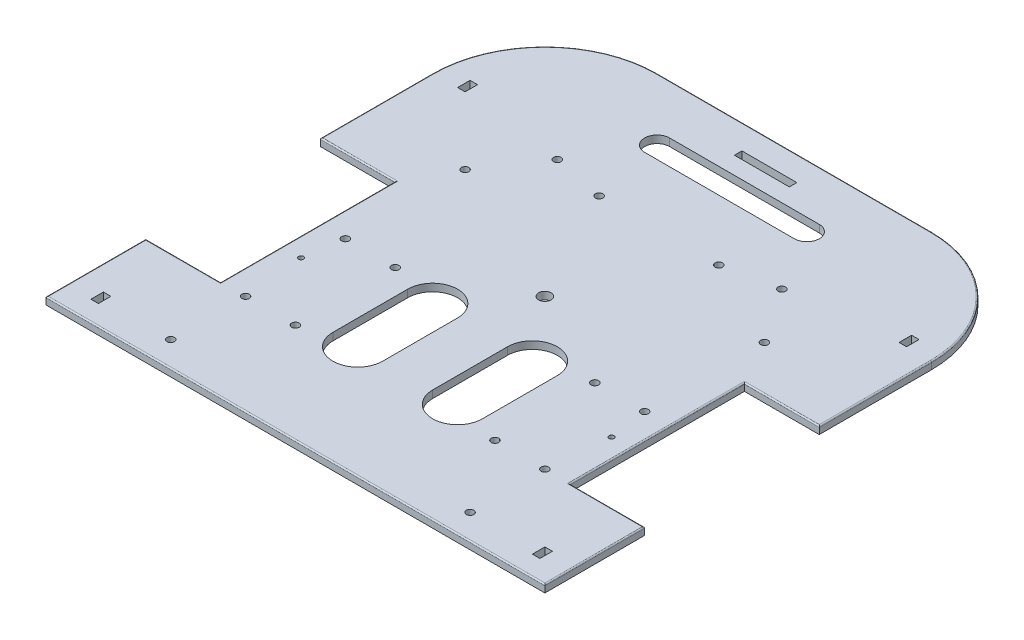
SolidWorks part; units mm, degrees
ref_plane "Front" through (0, 0, 0) normal (0, 0, 1) x (1, 0, 0)
ref_plane "Top" through (0, 0, 0) normal (0, 1, 0) x (1, 0, 0)
ref_plane "Right" through (0, 0, 0) normal (1, 0, 0) x (0, 0, -1)
sketch "Sketch1" plane through (0, 0, 0) normal (0, 1, 0) x (1, 0, 0)
  line L1 (100, -100) -> (-100, -100)
  line L2 (100, -100) -> (100, 100)
  line L3 (100, 100) -> (-100, 100)
  line L4 (-100, -100) -> (-100, 100)
  line L5 (100, -100) -> (-100, 100) construction
  line L6 (100, 100) -> (-100, -100) construction
  point P0 (0, 0)
  dimension "D1" = 200
  dimension "200mm" = 200
extrude "Boss-Extrude1" add sketch "Sketch1" along normal blind 3
ref_plane "Plane1" through (0, 0, 0) normal (1, 0, 0) x (0, 0, -1)
sketch "Sketch2" plane through (0, 3, 0) normal (0, 1, 0) x (1, 0, 0)
  line L0 (-100, 100) -> (-100, -100) construction
  line L1 (-70, 10) -> (-100, 10)
  line L2 (-70, 10) -> (-70, -60)
  line L3 (-70, -60) -> (-100, -60)
  line L4 (-100, 10) -> (-100, -60)
  line L5 (-100, -100) -> (100, -100) construction
  dimension "D1" = 40
  dimension "D2" = 30
  dimension "50" = 70
extrude "Cut-Extrude1" cut sketch "Sketch2" against normal through all and the other way blind 10
sketch "Sketch4" plane through (0, 3, 0) normal (0, 1, 0) x (1, 0, 0)
  line L1 (-87, -92) -> (-90, -92)
  line L2 (-87, -92) -> (-87, -87)
  line L3 (-87, -87) -> (-90, -87)
  line L4 (-90, -92) -> (-90, -87)
  line L5 (-87, -92) -> (-90, -87) construction
  line L6 (-87, -87) -> (-90, -92) construction
  line L7 (-100, -100) -> (100, -100) construction
  line L10 (-100, -60) -> (-100, -100) construction
  dimension "D1" = 5
  dimension "D2" = 3
  dimension "D3" = 10
  dimension "D4" = 8
  dimension "D5" = 5
  dimension "D6" = 5
extrude "Cut-Extrude2" cut sketch "Sketch4" against normal through all
sketch "Sketch5" plane through (0, 3, 0) normal (0, 1, 0) x (1, 0, 0)
  line L0 (-100, 100) -> (-100, 10) construction
  line L1 (-90, 55) -> (-87, 55)
  line L2 (-90, 55) -> (-90, 60)
  line L3 (-90, 60) -> (-87, 60)
  line L4 (-87, 55) -> (-87, 60)
  line L5 (-90, 55) -> (-87, 60) construction
  line L6 (-90, 60) -> (-87, 55) construction
  line L7 (-70, 10) -> (-100, 10) construction
  dimension "D1" = 5
  dimension "D2" = 3
  dimension "D3" = 10
  dimension "D4" = 45
extrude "Cut-Extrude3" cut sketch "Sketch5" against normal through all
sketch "Sketch7" plane through (0, 3, 0) normal (0, 1, 0) x (1, 0, 0)
  line L0 (-20, -55) -> (-20, -25) construction
  line L1 (-30, -55) -> (-30, -25)
  line L2 (-10, -55) -> (-10, -25)
  line L3 (-70, -60) -> (-70, 10) construction
  line L4 (-100, -100) -> (100, -100) construction
  arc A0 (-30, -55) -> (-10, -55) centre (-20, -55) ccw
  arc A1 (-10, -25) -> (-30, -25) centre (-20, -25) ccw
  point P2 (-20, -40)
  dimension "D2" = 10
  dimension "D4" = 30
  dimension "D1" = 30
  dimension "D3" = 50
  dimension "D5" = 60
extrude "Cut-Extrude4" cut sketch "Sketch7" against normal through all
fillet "Fillet1" radius 45 2 edges at (100, 1.5, -100) (-100, 1.5, -100)
sketch "Sketch9" plane through (0, 3, 0) normal (0, 1, 0) x (1, 0, 0)
  line L0 (-100, -60) -> (-100, -100) construction
  line L1 (-100, -100) -> (100, -100) construction
  line L2 (-30, 75) -> (30, 75) construction
  line L3 (-30, 80) -> (30, 80)
  line L4 (-30, 70) -> (30, 70)
  line L5 (-100, 55) -> (-100, 10) construction
  line L6 (55, 100) -> (-55, 100) construction
  line L8 (11, 90) -> (-11, 90)
  line L9 (11, 90) -> (11, 87)
  line L10 (11, 87) -> (-11, 87)
  line L11 (-11, 90) -> (-11, 87)
  line L12 (11, 90) -> (-11, 87) construction
  line L13 (11, 87) -> (-11, 90) construction
  circle A0 centre (-60, -90) radius 1.5
  arc A1 (-30, 80) -> (-30, 70) centre (-30, 75) ccw
  arc A2 (30, 70) -> (30, 80) centre (30, 75) ccw
  point P8 (0, 75)
  point P17 (0, 88.5)
  dimension "D1" = 3
  dimension "D6" = 5
  dimension "D2" = 40
  dimension "D3" = 10
  dimension "D4" = 60
  dimension "D5" = 100
  dimension "D7" = 20
  dimension "D9" = 22
  dimension "D10" = 3
  dimension "D11" = 100
  dimension "D12" = 10
sketch "Sketch10" plane through (0, 3, 0) normal (0, 1, 0) x (1, 0, 0)
  line L0 (-100, -60) -> (-100, -100) construction
  line L1 (-100, -100) -> (100, -100) construction
  circle A0 centre (-60, -60) radius 1.5
  dimension "D1" = 3
  dimension "D2" = 40
  dimension "D3" = 40
sketch "Sketch11" plane through (0, 3, 0) normal (0, 1, 0) x (1, 0, 0)
  line L0 (55, 100) -> (-55, 100) construction
  line L1 (-100, 55) -> (-100, 10) construction
  circle A0 centre (-45, 50) radius 1.5
  dimension "D1" = 3
  dimension "D2" = 50
  dimension "D3" = 55
extrude "Cut-Extrude7" cut sketch "Sketch9" against normal through all
extrude "Cut-Extrude8" cut sketch "Sketch11" against normal through all
extrude "Cut-Extrude9" cut sketch "Sketch10" against normal through all
pattern_linear "LPattern1" count 2 spacing 40 along (0, 0, -1) count 2 spacing 20 along (1, 0, 0) of "Cut-Extrude9"
sketch "Sketch13" plane through (0, 3, 0) normal (0, 1, 0) x (1, 0, 0)
  line L0 (-100, 55) -> (-100, 10) construction
  line L1 (55, 100) -> (-55, 100) construction
  circle A0 centre (-60, 28) radius 1.5
  dimension "D1" = 3
  dimension "D2" = 40
  dimension "D3" = 72
extrude "Cut-Extrude10" cut sketch "Sketch13" against normal through all
mirror "Mirror1" about plane through (0, 0, 0) normal (1, 0, 0) of "Cut-Extrude7", "Cut-Extrude10", "Cut-Extrude9", "Cut-Extrude8", "Cut-Extrude4", "Cut-Extrude3", "Cut-Extrude2", "Cut-Extrude1", "LPattern1"
fillet "Fillet2" radius 0.5 14 edges at (-86.8198, 3, -86.8198) (100, 3, -32.5) (86.8198, 3, -86.8198) (0, 3, -100) (85, 3, -10) (100, 3, 80) (85, 3, 60) (70, 3, 25) (0, 3, 100) (-100, 3, 80) (-85, 3, 60) (-100, 3, -32.5) (-85, 3, -10) (-70, 3, 25)
sketch "Sketch23" plane through (0, 0, 0) normal (0, -1, 0) x (1, 0, 0)
  line L0 (55, -100) -> (-55, -100) construction
  line L1 (10, -95.5) -> (-10, -95.5)
  line L2 (10, -95.5) -> (10, -90.4994)
  line L3 (10, -90.4994) -> (-10, -90.4994)
  line L4 (-10, -95.5) -> (-10, -90.4994)
  line L5 (10, -95.5) -> (-10, -90.4994) construction
  line L6 (10, -90.4994) -> (-10, -95.5) construction
  line L7 (-100, -55) -> (-100, -10) construction
  point P0 (0, -92.9997)
  dimension "D1" = 20
  dimension "D2" = 4.5
  dimension "D3" = 100
extrude "Boss-Extrude7" add sketch "Sketch23" along normal blind 10
sketch "Sketch26" plane through (0, 3, 0) normal (0, 1, 0) x (1, 0, 0)
  line L0 (0, 45.7414) -> (24, 45.7414) construction
  line L1 (0, -50) -> (0, 50) construction
  circle A0 centre (24, 45.7414) radius 1.5
  circle A1 centre (-24, 45.7414) radius 1.5
  dimension "D1" = 3
  dimension "D2" = 24
extrude "Cut-Extrude11" cut sketch "Sketch26" against normal blind 10
sketch "Sketch27" plane through (0, 3, 0) normal (0, 1, 0) x (1, 0, 0)
  circle A0 centre (0, 0) radius 2.5
  dimension "D1" = 5
extrude "Cut-Extrude12" cut sketch "Sketch27" against normal blind 10
sketch "Sketch28" plane through (0, 3, 0) normal (0, 1, 0) x (1, 0, 0)
  line L0 (-62.25, -99.5) -> (-62.25, -35.5) construction
  line L1 (-99.5, -99.5) -> (99.5, -99.5) construction
  line L2 (-62.25, -35.5) -> (-69.5, -35.5) construction
  line L3 (-69.5, 10.5) -> (-69.5, -60.5) construction
  line L4 (0, -50) -> (0, 50) construction
  circle A0 centre (-62.25, -35.5) radius 1
  circle A1 centre (62.25, -35.5) radius 1
  dimension "D3" = 2
  dimension "D1" = 64
  dimension "D2" = 7.25
extrude "Cut-Extrude13" cut sketch "Sketch28" against normal blind 10
